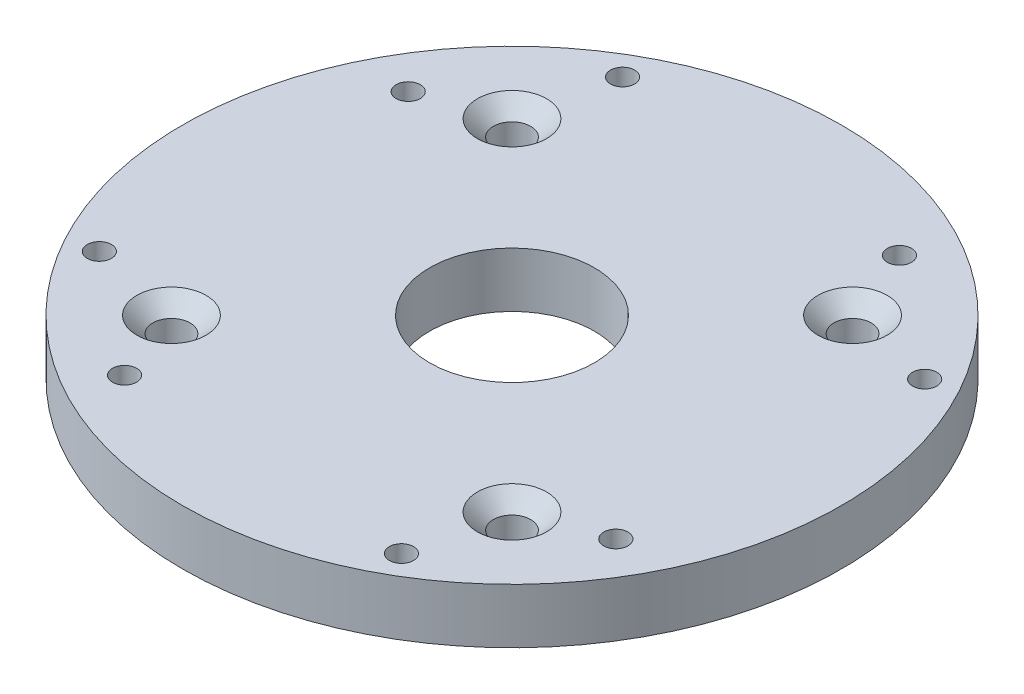
SolidWorks part; units mm, degrees
ref_plane "Ön Düzlem" through (0, 0, 0) normal (0, 0, 1) x (1, 0, 0)
ref_plane "Üst Düzlem" through (0, 0, 0) normal (0, 1, 0) x (1, 0, 0)
ref_plane "Sağ Düzlem" through (0, 0, 0) normal (1, 0, 0) x (0, 0, -1)
sketch "Sketch1" plane through (0, 0, 0) normal (0, 1, 0) x (1, 0, 0)
  circle A0 centre (0, 0) radius 30
  dimension "D1" = 60
extrude "Boss-Extrude1" add sketch "Sketch1" along normal blind 5
sketch "Sketch2" plane through (0, 5, 0) normal (0, 1, 0) x (1, 0, 0)
  line L1 (-15.5, -15.5) -> (15.5, -15.5) construction
  line L2 (-15.5, -15.5) -> (-15.5, 15.5) construction
  line L3 (-15.5, 15.5) -> (15.5, 15.5) construction
  line L4 (15.5, -15.5) -> (15.5, 15.5) construction
  line L5 (-15.5, -15.5) -> (15.5, 15.5) construction
  line L6 (-15.5, 15.5) -> (15.5, -15.5) construction
  point P7 (15.5, 15.5)
  point P8 (-15.5, 15.5)
  point P9 (15.5, -15.5)
  point P10 (-15.5, -15.5)
  point P11 (0, 0)
  dimension "D1" = 31
hole_wizard "CSK for M3 Flat Head Machine Screw1" positions "Sketch2" profile "Sketch3" countersink size "M3" standard "ANSI Metric" end condition through all
sketch "Sketch3" plane through (-15.5, 5, 15.5) normal (1, 0, 0) x (0, 0, 1)
  line L0 (0, 0) -> (0, 5)
  line L1 (0, 5) -> (1.7, 5)
  line L2 (1.7, 5) -> (1.7, 1.45)
  line L3 (1.7, 1.45) -> (3.15, 0)
  line L5 (3.15, 0) -> (0, 0)
  line L6 (-1.7, 1.45) -> (-3.15, 0) construction
  line L11 (0, -6.35) -> (0, 107.95) construction
  dimension "Thru Hole Dia." = 3.4
  dimension "Thru Hole Depth" = 5
  dimension "Near C'Sink Dia." = 6.3
  dimension "Near C'Sink Angle" = 90
sketch "Sketch4" plane through (0, 5, 0) normal (0, 1, 0) x (1, 0, 0)
  line L0 (0, -32.1268) -> (0, 32.1268) construction
  line L1 (-32.2835, 0) -> (32.2835, 0) construction
  line L2 (0, 0) -> (-16.4059, 28.4159) construction
  circle A0 centre (-13.75, 23.8157) radius 1.1
  circle A1 centre (-22.36, 12.9096) radius 1.1
  circle A2 centre (12.9096, 22.36) radius 1.1
  circle A3 centre (23.8157, 13.75) radius 1.1
  circle A4 centre (22.36, -12.9096) radius 1.1
  circle A5 centre (13.75, -23.8157) radius 1.1
  circle A6 centre (-12.9096, -22.36) radius 1.1
  circle A7 centre (-23.8157, -13.75) radius 1.1
  point P4 (0, 0)
  point P8 (0, 0)
  point P16 (1.9983, 2.5313)
  point P29 (0, 0)
  dimension "D2" = 2.2
  dimension "D5" = 27.5
  dimension "D1" = 30
  dimension "D3" = 2
  dimension "D4" = 4
extrude "Cut-Extrude1" cut sketch "Sketch4" against normal up to next
sketch "Sketch5" plane through (0, 5, 0) normal (0, 1, 0) x (1, 0, 0)
  circle A0 centre (0, 0) radius 7.5
  dimension "D1" = 15
extrude "Cut-Extrude2" cut sketch "Sketch5" against normal up to next
